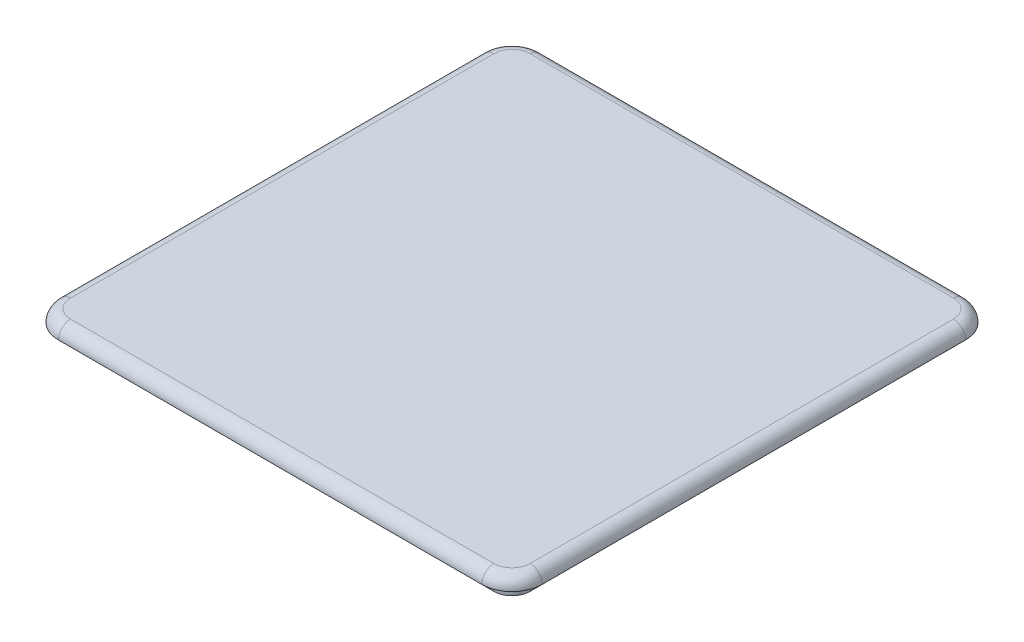
SolidWorks part; units mm, degrees
ref_plane "Front Plane" through (0, 0, 0) normal (0, 0, 1) x (1, 0, 0)
ref_plane "Top Plane" through (0, 0, 0) normal (0, 1, 0) x (1, 0, 0)
ref_plane "Right Plane" through (0, 0, 0) normal (1, 0, 0) x (0, 0, -1)
sketch "Sketch1" plane through (0, 0, 0) normal (0, 1, 0) x (1, 0, 0)
  line L1 (-44.45, 50.8) -> (44.45, 50.8)
  line L2 (-50.8, 44.45) -> (-50.8, -44.45)
  line L3 (-44.45, -50.8) -> (44.45, -50.8)
  line L4 (50.8, 44.45) -> (50.8, -44.45)
  arc A0 (-50.8, -44.45) -> (-44.45, -50.8) centre (-44.45, -44.45) ccw
  arc A1 (44.45, -50.8) -> (50.8, -44.45) centre (44.45, -44.45) ccw
  arc A2 (50.8, 44.45) -> (44.45, 50.8) centre (44.45, 44.45) ccw
  arc A3 (-44.45, 50.8) -> (-50.8, 44.45) centre (-44.45, 44.45) ccw
  point P7 (-210.6432, 135.2806)
  point P8 (-50.8, -50.8)
  point P13 (50.8, 50.8)
  point P16 (-50.8, 50.8)
  dimension "D5" = 6.35
  dimension "D1" = 101.6
  dimension "D2" = 101.6
  dimension "D3" = 50.8
  dimension "D4" = 50.8
extrude "Boss-Extrude1" add sketch "Sketch1" along normal blind 2.54
sketch "Sketch2" plane through (0, 0, 0) normal (0, -1, 0) x (1, 0, 0)
  line L8 (-48.26, 44.45) -> (-48.26, -44.45)
  line L9 (-44.45, -48.26) -> (44.45, -48.26)
  line L10 (48.26, -44.45) -> (48.26, 44.45)
  line L11 (44.45, 48.26) -> (-44.45, 48.26)
  line L12 (-48.26, 44.45) -> (-48.26, -44.45)
  line L13 (-44.45, -48.26) -> (44.45, -48.26)
  line L14 (48.26, -44.45) -> (48.26, 44.45)
  line L15 (44.45, 48.26) -> (-44.45, 48.26)
  arc A8 (-44.45, 48.26) -> (-48.26, 44.45) centre (-44.45, 44.45) ccw
  arc A9 (-48.26, -44.45) -> (-44.45, -48.26) centre (-44.45, -44.45) ccw
  arc A10 (44.45, -48.26) -> (48.26, -44.45) centre (44.45, -44.45) ccw
  arc A11 (48.26, 44.45) -> (44.45, 48.26) centre (44.45, 44.45) ccw
  arc A12 (-44.45, 48.26) -> (-48.26, 44.45) centre (-44.45, 44.45) ccw
  arc A13 (-48.26, -44.45) -> (-44.45, -48.26) centre (-44.45, -44.45) ccw
  arc A14 (44.45, -48.26) -> (48.26, -44.45) centre (44.45, -44.45) ccw
  arc A15 (48.26, 44.45) -> (44.45, 48.26) centre (44.45, 44.45) ccw
  dimension "D1" = 2.54
extrude "Boss-Extrude2" add sketch "Sketch2" along normal blind 2.54
ref_plane "Plane1" through (0, 0, 0) normal (-1, 0, 0) x (0, 0, 1)
ref_plane "Plane2" through (0, 0, 0) normal (0, 0, -1) x (-1, 0, 0)
fillet "Fillet1" radius 2.54 8 edges at (48.9401, 2.54, -48.9401) (50.8, 2.54, 0) (48.9401, 2.54, 48.9401) (0, 2.54, 50.8) (-48.9401, 2.54, 48.9401) (-50.8, 2.54, 0) (-48.9401, 2.54, -48.9401) (0, 2.54, -50.8)
